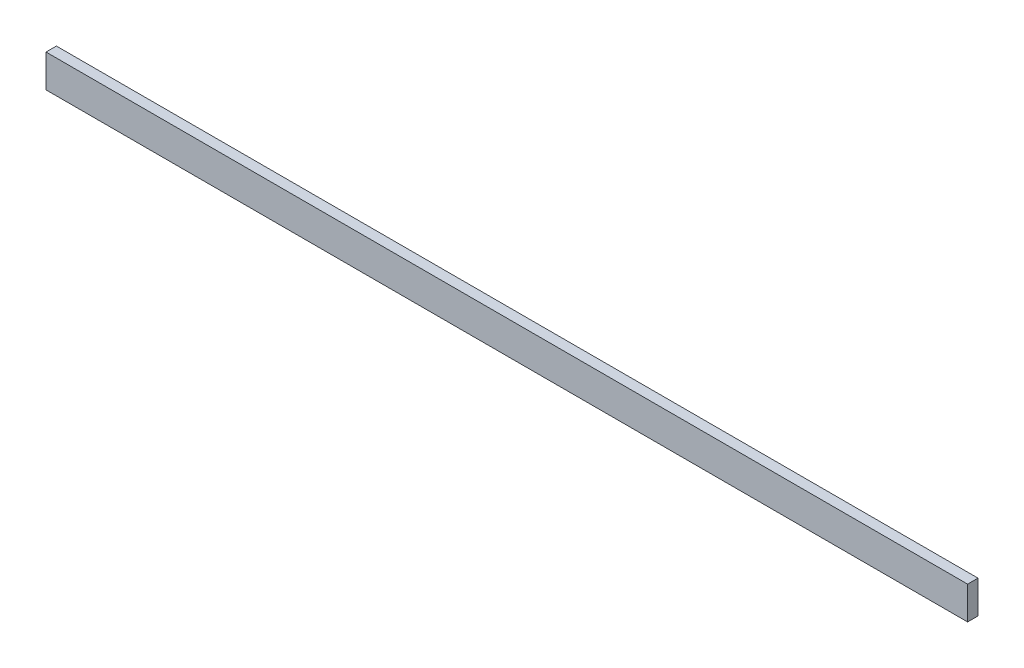
SolidWorks part; units mm, degrees
ref_plane "Front" through (0, 0, 0) normal (0, 0, 1) x (1, 0, 0)
ref_plane "Top" through (0, 0, 0) normal (0, 1, 0) x (1, 0, 0)
ref_plane "Right" through (0, 0, 0) normal (1, 0, 0) x (0, 0, -1)
sketch "Sketch1" plane through (0, 0, 0) normal (0, 1, 0) x (1, 0, 0)
  line L0 (1686.8, 9.5) -> (1686.8, -9.5) construction
  line L1 (1686.8, 9.5) -> (0, 9.5)
  line L2 (1686.8, 9.5) -> (1686.8, -9.5)
  line L3 (1686.8, -9.5) -> (0, -9.5)
  line L4 (0, 9.5) -> (0, -9.5)
  line L5 (1686.8, 9.5) -> (0, -9.5) construction
  line L6 (1686.8, -9.5) -> (0, 9.5) construction
  point P0 (843.4, 0)
  dimension "D1" = 19
extrude "Boss-Extrude1" add sketch "Sketch1" along normal blind 60
